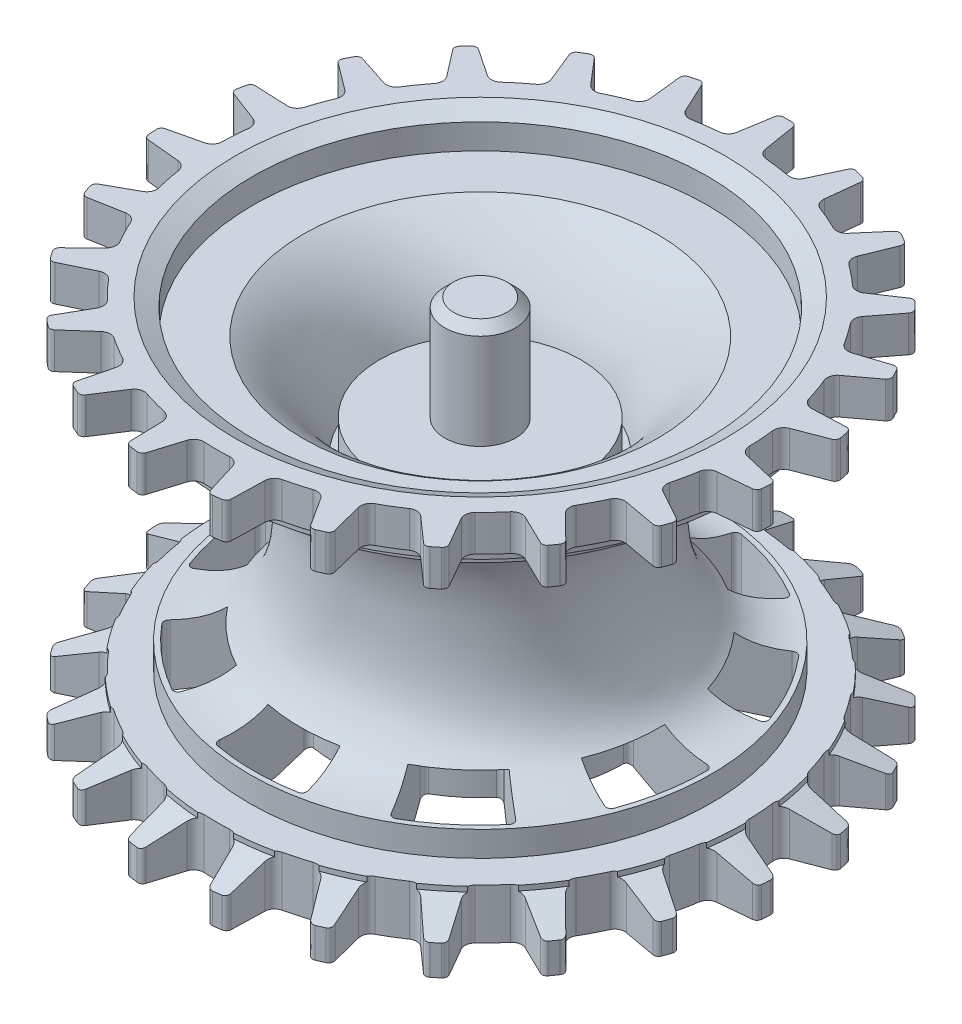
SolidWorks part; units mm, degrees
ref_plane "Front Plane" through (0, 0, 0) normal (0, 0, 1) x (1, 0, 0)
ref_plane "Top Plane" through (0, 0, 0) normal (0, 1, 0) x (1, 0, 0)
ref_plane "Right Plane" through (0, 0, 0) normal (1, 0, 0) x (0, 0, -1)
sketch "Sketch2" plane through (0, 0, 0) normal (0, 0, 1) x (1, 0, 0)
  line L0 (0, 1.05) -> (0, 14.85)
  line L1 (0, 14.85) -> (1.0564, 14.85)
  line L2 (1.0564, 14.85) -> (1.41, 14.4964)
  line L3 (1.41, 14.4964) -> (1.41, 10.6964)
  line L4 (1.41, 10.6964) -> (4, 10.6964)
  line L5 (4, 10.6964) -> (4, 9.4235)
  line L6 (4, 9.4235) -> (4.25, 9.4235)
  line L7 (0, 1.05) -> (0.4, 1.05)
  line L8 (0.4, 1.05) -> (0.4, 1.8)
  line L9 (0.4, 1.8) -> (2, 1.8)
  line L10 (2, 1.8) -> (2, 2)
  line L11 (2, 2) -> (5.15, 2)
  line L12 (5.15, 2) -> (6.9, 0.9896)
  line L13 (6.9, 0.9896) -> (9.2, 0.5)
  line L14 (9.2, 0.5) -> (10.3, 0.5)
  line L15 (10.3, 0.5) -> (10.3, 0)
  line L16 (10.3, 0) -> (12.25, 0)
  line L17 (12.25, 0) -> (12.25, 1.2)
  line L18 (12.25, 1.2) -> (10.5634, 1.8)
  line L19 (10.5634, 1.8) -> (10.5634, 2)
  line L20 (10.5634, 2) -> (9.2, 2)
  line L21 (9.2, 2) -> (9.2, 3)
  line L22 (7.05, 13.4964) -> (9.05, 13.4964)
  line L23 (9.05, 13.4964) -> (9.05, 14.4964)
  line L24 (9.05, 14.4964) -> (9.75, 14.85)
  line L25 (9.75, 14.85) -> (12.25, 14.85)
  line L26 (12.25, 14.85) -> (12.25, 13.41)
  line L27 (12.25, 13.41) -> (10.33, 13.41)
  line L28 (10.33, 13.41) -> (10.33, 13.11)
  line L29 (10.33, 13.11) -> (9.33, 13.11)
  line L30 (9.33, 13.11) -> (9.33, 12.286)
  line L31 (5.8, 7.95) -> (-1.8039, 7.95) construction
  line L32 (1.1054, 0) -> (0, 0) construction
  line L33 (7.6716, 12.286) -> (8.5646, 12.286) construction
  line L34 (5.7998, 6.1198) -> (5.7998, 9.0842) construction
  line L35 (9.2, 0.5) -> (9.2, 1.2121) construction
  line L36 (10.8632, 3) -> (6.0632, 3) construction
  arc A0 (4.25, 9.4235) -> (7.05, 13.4964) centre (10.1555, 8.3626) cw
  spline S0 degree 3 poles (9.33, 12.286) (6.33, 12.286) (5.7497, 9.0699) (5.8685, 5.9809) (6.2, 3) (9.2, 3) knots 0 0 0 0 0.33945 0.43945 1 1 1 1
  point P40 (12.25, 0.6)
  dimension "D17" = 6
  dimension "D22" = 5.8
  dimension "D23" = 10
  dimension "D24" = 10
  dimension "D1" = 7.95
  dimension "D2" = 6.9
  dimension "D3" = 0.4
  dimension "D4" = 2
  dimension "D5" = 0.2
  dimension "D6" = 5.15
  dimension "D7" = 1.75
  dimension "150" = 150
  dimension "2" = 2
  dimension "D8" = 1.1
  dimension "D9" = 1.2
  dimension "0.5" = 0.5
  dimension "10.30" = 10.3
  dimension "D10" = 1.8
  dimension "D11" = 0.2
  dimension "D12" = 12.25
  dimension "D13" = 1
  dimension "D14" = 0.5
  dimension "D15" = 45
  dimension "D16" = 1.41
  dimension "3.8" = 3.8
  dimension "D18" = 4.25
  dimension "D19" = 0.7
  dimension "D20" = 2
  dimension "D21" = 1
  dimension "2.5" = 2.5
  dimension "4" = 4
  dimension "D25" = 0.3
  dimension "D26" = 1
  dimension "D27" = 1.44
  dimension "D28" = 0.75
  dimension "D29" = 1.92
revolve "Revolve1" add sketch "Sketch2" angle 360 about L0
sketch "Sketch3" plane through (0, 0, 0) normal (0, -1, 0) x (1, 0, 0)
  line L0 (0, 0) -> (-1.8, 8.8182)
  line L1 (-1.8, 8.8182) -> (0, 0)
  line L2 (0, 0) -> (1.8, 8.8182)
  line L3 (0, 0) -> (0, 16.9171) construction
  circle A0 centre (0, 0) radius 9
  circle A1 centre (0, 0) radius 5.75
  point P7 (-2.3499, 8.8948)
  point P9 (0, 0)
  point P10 (0, 0)
  point P11 (-1.2856, 8.6973)
  dimension "D1" = 3.6
  dimension "D2" = 18
  dimension "D3" = 11.5
extrude "Cut-Extrude1" cut sketch "Sketch3" against normal blind 3.6 contours A1 L3 A0 L1 | L3 A1 L2 A0
fillet "Fillet1" radius 0.2 4 edges at (-1.15, 2.6268, 5.6338) (-1.8, 1.7732, 8.8182) (1.8, 1.7732, 8.8182) (1.15, 2.6268, 5.6338)
pattern_circular "CirPattern1" count 9 over 360 about axis through (0, 0, 0) along (0, 1, 0) of "Cut-Extrude1", "Fillet1"
sketch "Sketch4" plane through (0, 0, 0) normal (0, -1, 0) x (1, 0, 0)
  line L0 (0, 0) -> (0, 12.25) construction
  line L1 (-0.9013, 10.7698) -> (-1.335, 12.177)
  line L2 (0.9013, 10.7698) -> (1.335, 12.177)
  circle A0 centre (0, 0) radius 12.25
  circle A1 centre (0, 0) radius 10.5
  arc A2 (-0.5, 10.4881) -> (-0.9013, 10.7698) centre (-0.519, 10.8876) cw
  arc A3 (0.5, 10.4881) -> (0.9013, 10.7698) centre (0.519, 10.8876) ccw
  point P5 (-1.5251, 10.8884)
  circle M3 centre (0, 0) radius 12.25
  dimension "D1" = 24.5
  dimension "D2" = 21
  dimension "D3" = 0.4
  dimension "D4" = 2.67
  dimension "D5" = 1
extrude "Cut-Extrude2" cut sketch "Sketch4" against normal blind 16 contours L0 A1 A3 L2 M3 | A1 L0 A0 L1 A2
fillet "Fillet2" radius 0.2 4 edges at (1.335, 0.6, 12.177) (-1.335, 0.6, 12.177) (1.335, 14.13, 12.177) (-1.335, 14.13, 12.177)
pattern_circular "CirPattern2" count 23 over 360 about axis through (0, 0, 0) along (0, 1, 0) of "Cut-Extrude2", "Fillet2"
sketch "Sketch6" plane through (0, 2, 0) normal (0, -1, 0) x (1, 0, 0)
  circle A0 centre (0, 0) radius 3 construction
  circle A1 centre (0, 3) radius 0.4
  circle A2 centre (2.8532, 0.9271) radius 0.4
  circle A3 centre (1.7634, -2.4271) radius 0.4
  circle A4 centre (-1.7634, -2.4271) radius 0.4
  circle A5 centre (-2.8532, 0.9271) radius 0.4
  point P16 (0, 0)
  dimension "D1" = 5
extrude "Boss-Extrude2" add sketch "Sketch6" along normal blind 1
chamfer "Chamfer1" distance 0.2 angle 45 5 edges at (1.7634, 1, -2.8271) (-1.7634, 1, -2.8271) (-2.8532, 1, 0.5271) (2.8532, 1, 0.5271) (0, 1, 2.6)
sketch "Sketch7" plane through (0, 0.5, 0) normal (0, -1, 0) x (1, 0, 0)
  circle A0 centre (0, 0) radius 9.65 construction
  circle A1 centre (0, 9.65) radius 0.4
  dimension "D1" = 19.3
  dimension "D2" = 0.8
extrude "Boss-Extrude3" add sketch "Sketch7" along normal blind 0.5
pattern_circular "CirPattern3" count 23 over 360 about axis through (0, 0, 0) along (0, 1, 0) of "Boss-Extrude3"
